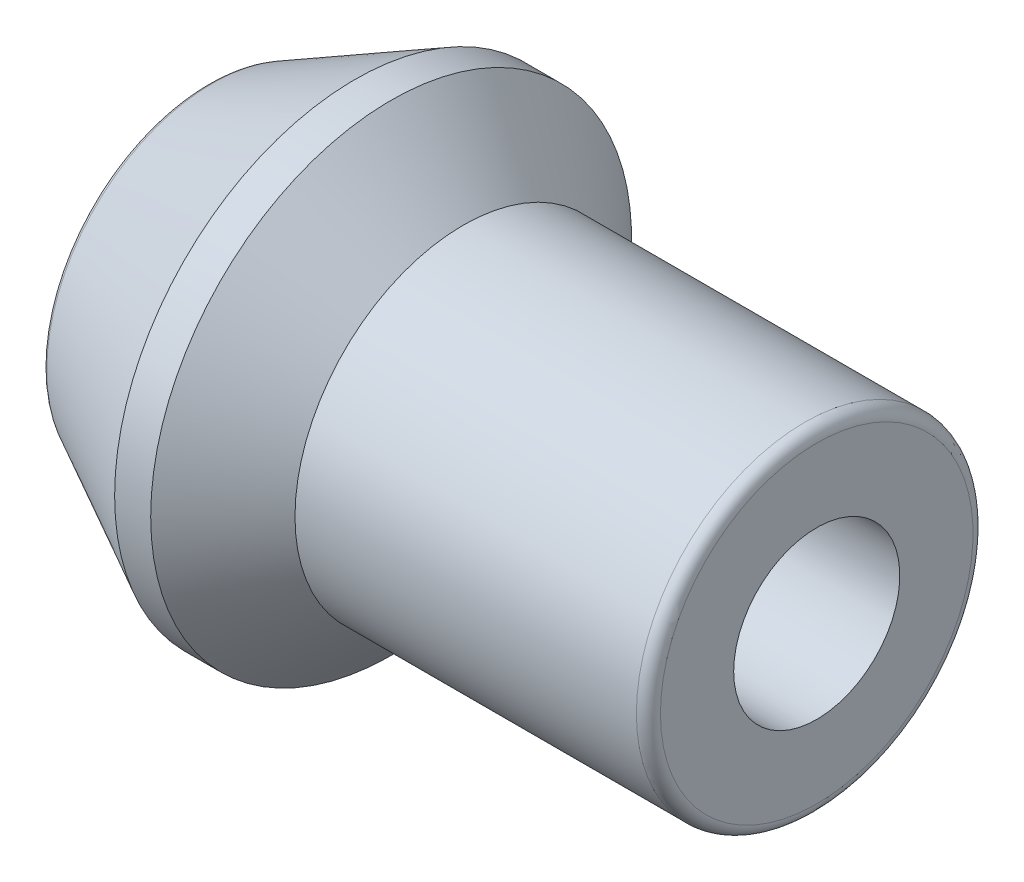
SolidWorks part; units mm, degrees
material "AISI 1045 Steel, cold drawn"
ref_plane "Front Plane" through (0, 0, 0) normal (0, 0, 1) x (1, 0, 0)
ref_plane "Top Plane" through (0, 0, 0) normal (0, 1, 0) x (1, 0, 0)
ref_plane "Right Plane" through (0, 0, 0) normal (1, 0, 0) x (0, 0, -1)
sketch "Sketch1" plane through (0, 0, 0) normal (0, 0, 1) x (1, 0, 0)
  line L0 (-16.6647, 0) -> (18.6597, 0) construction
  line L1 (0, 0) -> (0, 6.4476)
  line L2 (0.2679, 6.8904) -> (6.2, 10)
  line L3 (6.2, 10) -> (7.7, 10)
  line L4 (7.7, 10) -> (10.7, 7)
  line L5 (10.7, 7) -> (24.9, 7)
  line L6 (25.4, 6.5) -> (25.4, 0)
  line L9 (25.4, 0) -> (0, 0)
  arc A0 (0, 6.4476) -> (0.2679, 6.8904) centre (0.5, 6.4476) cw
  arc A1 (24.9, 7) -> (25.4, 6.5) centre (24.9, 6.5) cw
  point P15 (6.95, 10)
  point P18 (0, 6.75)
  point P21 (25.4, 7)
  dimension "D7" = 0.5
  dimension "D8" = 0.5
  dimension "D1" = 25.4
  dimension "D2" = 13.5
  dimension "D3" = 14.7
  dimension "D4" = 1.5
  dimension "D5" = 20
  dimension "D6" = 14
  dimension "D9" = 135
revolve "Revolve1" add sketch "Sketch1" angle 360 about L0
hole_wizard "Tap Drill for 5/16-24 Tap1" positions "Sketch2" profile "Sketch4" hole size "5/16-24" standard "ANSI Inch" end condition up to next
sketch "Sketch2" plane through (0, 0, 0) normal (-1, 0, 0) x (0, 0, 1)
  point P0 (0, 0)
sketch "Sketch4" plane through (0, 0, 0) normal (0, 1, 0) x (0, 0, 1)
  line L0 (0, 0) -> (0, 25.4)
  line L1 (0, 25.4) -> (3.4544, 25.4)
  line L2 (3.4544, 25.4) -> (3.4544, 0)
  line L5 (3.4544, 0) -> (0, 0)
  line L11 (0, -6.35) -> (0, 107.95) construction
  dimension "Thru Hole Dia." = 6.9088
  dimension "Thru Hole Depth" = 25.4
equation "\"CA_ID\"= 14"
equation "\"D6@Sketch1\"=\"CA_ID\""
